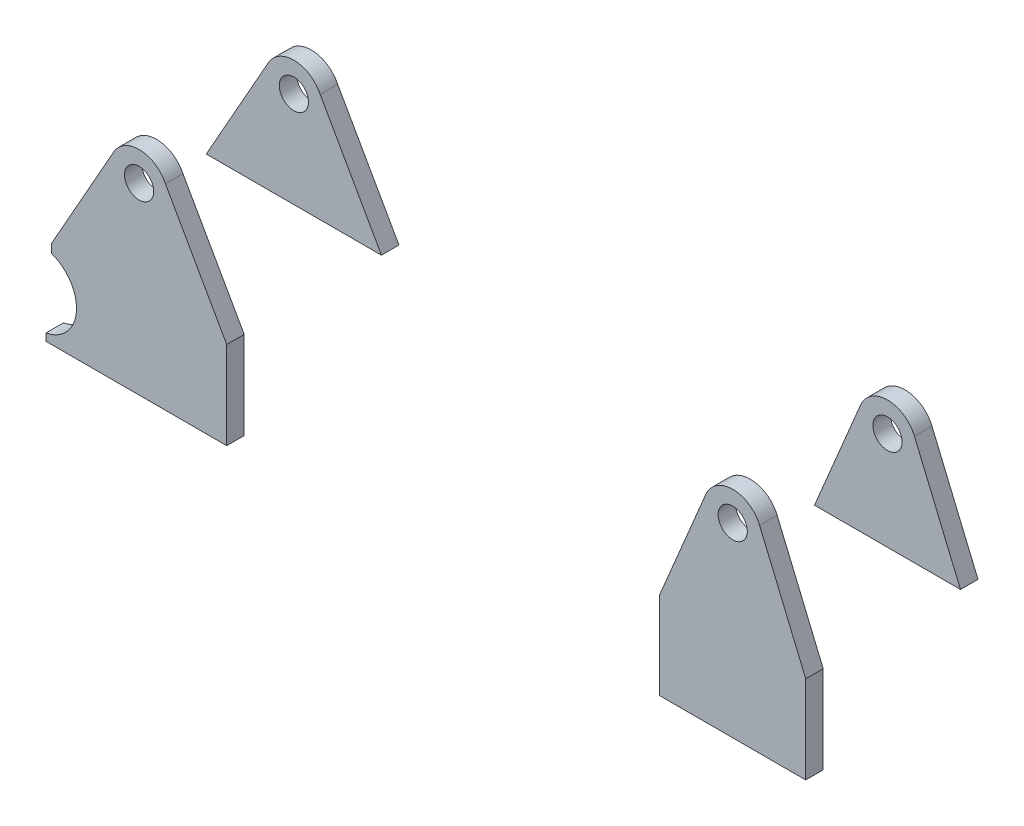
SolidWorks part; units mm, degrees
ref_plane "Front Plane" through (0, 0, 0) normal (0, 0, 1) x (1, 0, 0)
ref_plane "Top Plane" through (0, 0, 0) normal (0, 1, 0) x (1, 0, 0)
ref_plane "Right Plane" through (0, 0, 0) normal (1, 0, 0) x (0, 0, -1)
sketch "Sketch1" plane through (0, 0, 0) normal (0, 0, 1) x (1, 0, 0)
  line L0 (-745.1446, -553.3409) -> (-146.7576, -553.3409) construction
  line L1 (-745.1446, -553.3409) -> (-146.7576, -553.3409)
  line L2 (-737.4286, -553.3409) -> (-716.1399, -515.5758)
  line L3 (-698.3946, -516.1984) -> (-677.4286, -553.3409)
  line L4 (-711.9899, -518.4382) -> (-702.8674, -522.5346) construction
  line L5 (-500.2511, -516.4563) -> (-508.0021, -522.7748) construction
  line L6 (-707.4286, -520.4864) -> (-707.4286, -553.3409) construction
  line L7 (-513.3474, -515.7455) -> (-529.1266, -553.3409)
  line L9 (-494.9058, -515.7455) -> (-479.1266, -553.3409)
  line L11 (-745.1446, -583.3409) -> (-146.7581, -583.3409) construction
  line L12 (-739.3147, -583.3409) -> (-146.7581, -583.3409)
  line L16 (-677.4286, -553.3409) -> (-677.4286, -583.3409)
  line L17 (-737.4286, -553.3409) -> (-737.4286, -556.3319)
  line L19 (-504.1266, -519.6156) -> (-504.1266, -553.3409) construction
  line L20 (-529.1266, -553.3409) -> (-529.1266, -583.3409)
  line L21 (-529.1266, -583.3409) -> (-479.1266, -583.3409)
  line L22 (-479.1266, -583.3409) -> (-479.1266, -553.3409)
  line L23 (-739.3147, -580.8409) -> (-739.3147, -583.3409)
  circle A0 centre (-707.4286, -520.4864) radius 10
  circle A2 centre (-504.1266, -519.6156) radius 10
  arc A3 (-728.8602, -568.341) -> (-754.2602, -568.341) centre (-741.5602, -568.341) ccw
  arc A4 (-728.8602, -568.341) -> (-737.4286, -556.3319) centre (-741.5602, -568.341) ccw
  arc A5 (-754.2602, -568.341) -> (-728.8602, -568.341) centre (-741.5602, -568.341) ccw
  arc A6 (-739.3147, -580.8409) -> (-728.8602, -568.341) centre (-741.5602, -568.341) ccw
  spline S1 degree 3 poles (-702.4287, -520.5174) (-702.3667, -510.5176) (-712.3665, -510.4556) (-712.4285, -520.4554) (-712.4906, -530.4552) (-702.4908, -530.5172) (-702.4287, -520.5174) (-702.3667, -510.5176) (-712.3665, -510.4556) knots -0.5 0 0 0 0.5 0.5 0.5 1 1 1 1.5 1.5 1.5 weights 1 0.333333 0.333333 1 0.333333 0.333333 1 0.333333 0.333333 only from (-702.4287, -520.5174) to (-702.4287, -520.5174) construction
  spline S2 degree 3 poles (-499.1267, -519.6466) (-499.0647, -509.6468) (-509.0645, -509.5847) (-509.1265, -519.5845) (-509.1886, -529.5843) (-499.1887, -529.6464) (-499.1267, -519.6466) (-499.0647, -509.6468) (-509.0645, -509.5847) knots -0.5 0 0 0 0.5 0.5 0.5 1 1 1 1.5 1.5 1.5 weights 1 0.333333 0.333333 1 0.333333 0.333333 1 0.333333 0.333333 only from (-499.1267, -519.6466) to (-499.1267, -519.6466) construction
  spline S3 degree 3 poles (-702.4287, -520.5174) (-702.3667, -510.5176) (-712.3665, -510.4556) (-712.4285, -520.4554) (-712.4906, -530.4552) (-702.4908, -530.5172) (-702.4287, -520.5174) (-702.3667, -510.5176) (-712.3665, -510.4556) knots -0.5 0 0 0 0.5 0.5 0.5 1 1 1 1.5 1.5 1.5 weights 1 0.333333 0.333333 1 0.333333 0.333333 1 0.333333 0.333333 only from (-702.4287, -520.5174) to (-702.4287, -520.5174)
  spline S4 degree 3 poles (-499.1267, -519.6466) (-499.0647, -509.6468) (-509.0645, -509.5847) (-509.1265, -519.5845) (-509.1886, -529.5843) (-499.1887, -529.6464) (-499.1267, -519.6466) (-499.0647, -509.6468) (-509.0645, -509.5847) knots -0.5 0 0 0 0.5 0.5 0.5 1 1 1 1.5 1.5 1.5 weights 1 0.333333 0.333333 1 0.333333 0.333333 1 0.333333 0.333333 only from (-499.1267, -519.6466) to (-499.1267, -519.6466)
  point P4 (-707.4286, -520.4864)
  point P13 (-707.4286, -520.4864)
  point P16 (-504.1266, -519.6156)
  dimension "D1" = 20
  dimension "D2" = 30
  dimension "D4" = 20
  dimension "D3" = 30
  dimension "D5" = 25
  dimension "D6" = 25
extrude "Boss-Extrude1" add sketch "Sketch1" along normal blind 6 contours L1 L12 | L20 L1 | S4 | L1 L17 L12 L16 | A0 L2 L1 L3 | L3 A0 S3 region at (-707.4356, -541.1782, 0) region at (-705.1223, -568.3832, 0) region at (-707.0879, -510.7752, 0) region at (-504.1266, -540.8667, 0) region at (-504.1266, -568.3409, 0) region at (-504.1266, -509.8984, 0)
ref_plane "Plane1" through (0, 0, -47) normal (0, 0, -1) x (-1, 0, 0)
sketch "Sketch2" plane through (0, 0, -47) normal (0, 0, -1) x (-1, 0, 0)
  line L0 (745.1446, -553.3409) -> (146.7581, -553.3409) construction
  line L1 (745.1446, -553.3409) -> (146.7581, -553.3409)
  line L6 (737.4286, -556.3319) -> (737.4286, -553.3409)
  line L7 (737.4286, -553.3409) -> (716.1399, -515.5758)
  line L8 (698.3946, -516.1984) -> (677.4286, -553.3409)
  line L9 (677.4286, -553.3409) -> (677.4286, -583.3409)
  line L10 (677.4286, -583.3409) -> (739.3147, -583.3409)
  line L11 (739.3147, -583.3409) -> (739.3147, -580.8409)
  line L12 (737.4286, -556.3319) -> (737.4286, -553.3409)
  line L13 (737.4286, -553.3409) -> (716.1399, -515.5758)
  line L14 (698.3946, -516.1984) -> (677.4286, -553.3409)
  line L15 (677.4286, -553.3409) -> (677.4286, -583.3409)
  line L16 (677.4286, -583.3409) -> (739.3147, -583.3409)
  line L17 (739.3147, -583.3409) -> (739.3147, -580.8409)
  line L19 (479.1266, -583.3409) -> (529.1266, -583.3409)
  line L20 (529.1266, -583.3409) -> (529.1266, -553.3409)
  line L21 (529.1266, -553.3409) -> (513.3474, -515.7455)
  line L22 (494.9058, -515.7455) -> (479.1266, -553.3409)
  line L23 (479.1266, -553.3409) -> (479.1266, -583.3409)
  line L24 (479.1266, -583.3409) -> (529.1266, -583.3409)
  line L25 (529.1266, -583.3409) -> (529.1266, -553.3409)
  line L26 (529.1266, -553.3409) -> (513.3474, -515.7455)
  line L27 (494.9058, -515.7455) -> (479.1266, -553.3409)
  line L28 (479.1266, -553.3409) -> (479.1266, -583.3409)
  circle A0 centre (504.1266, -519.6156) radius 5 construction
  arc A1 (513.3474, -515.7455) -> (494.9058, -515.7455) centre (504.1266, -519.6156) ccw
  arc A2 (737.4286, -556.3319) -> (739.3147, -580.8409) centre (741.5602, -568.341) ccw
  arc A3 (716.1399, -515.5758) -> (698.3946, -516.1984) centre (707.4286, -520.4864) ccw
  arc A4 (737.4286, -556.3319) -> (739.3147, -580.8409) centre (741.5602, -568.341) ccw
  arc A5 (716.1399, -515.5758) -> (698.3946, -516.1984) centre (707.4286, -520.4864) ccw
  arc A6 (513.3474, -515.7455) -> (494.9058, -515.7455) centre (504.1266, -519.6156) ccw
  circle A7 centre (707.4286, -520.4864) radius 5 construction
  circle A8 centre (504.1266, -519.6156) radius 5
  circle A9 centre (707.4286, -520.4864) radius 5
  dimension "D1" = 0
  dimension "D2" = 0
extrude "Boss-Extrude2" add sketch "Sketch2" along normal blind 6 separate body contours L13 A5 L14 L1 A9 | L26 A6 L27 L1 A8 region at (-504.1266, -536.9841, -47) region at (-707.4345, -537.8062, -47)
